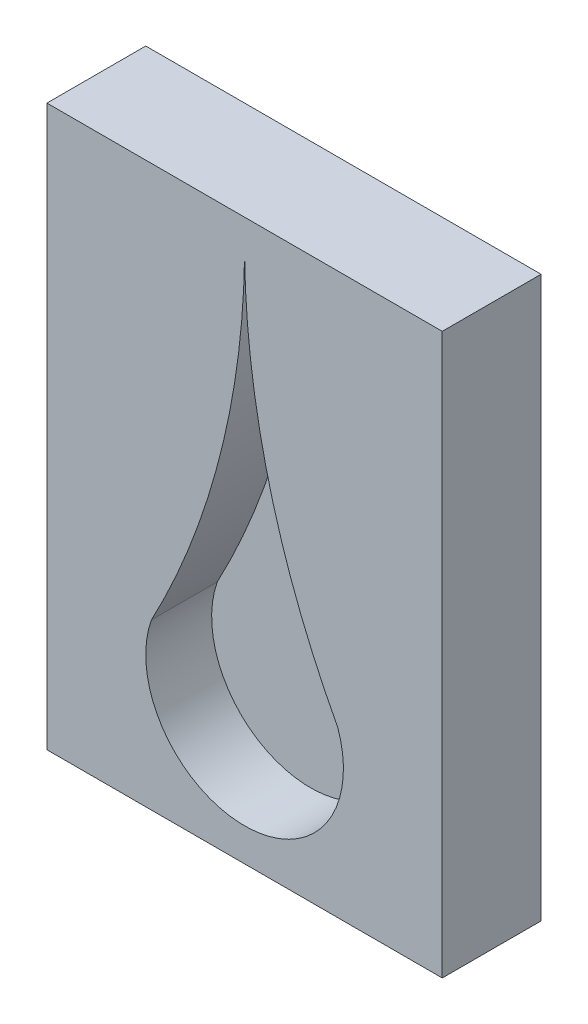
SolidWorks part; units mm, degrees
ref_plane "Front Plane" through (0, 0, 0) normal (0, 0, 1) x (1, 0, 0)
ref_plane "Top Plane" through (0, 0, 0) normal (0, 1, 0) x (1, 0, 0)
ref_plane "Right Plane" through (0, 0, 0) normal (1, 0, 0) x (0, 0, -1)
sketch "Sketch1" plane through (0, 0, 0) normal (0, 0, 1) x (1, 0, 0)
  line L1 (-38.1, -53.975) -> (38.1, -53.975)
  line L2 (-38.1, -53.975) -> (-38.1, 53.975)
  line L3 (-38.1, 53.975) -> (38.1, 53.975)
  line L4 (38.1, -53.975) -> (38.1, 53.975)
  line L5 (-38.1, -53.975) -> (38.1, 53.975) construction
  line L6 (-38.1, 53.975) -> (38.1, -53.975) construction
  point P0 (0, 0)
  dimension "D1" = 76.2
  dimension "D2" = 107.95
extrude "Boss-Extrude1" add sketch "Sketch1" along normal blind 19.05
sketch "Sketch2" plane through (0, 0, 19.05) normal (0, 0, 1) x (1, 0, 0)
  line L1 (0, 0) -> (0, 50000) construction
  line L3 (38.1, 53.975) -> (-38.1, 53.975) construction
  line L4 (-38.1, -53.975) -> (38.1, -53.975) construction
  line L5 (-38.1, 53.975) -> (-38.1, -53.975) construction
  line L6 (-17.9605, -22.225) -> (17.9605, -22.225) construction
  arc A0 (-17.9605, -22.225) -> (17.9605, -22.225) centre (0, -28.575) ccw
  arc A1 (-17.9605, -22.225) -> (0, 47.625) centre (-152.3875, 49.5743) ccw
  arc A2 (17.9605, -22.225) -> (0, 47.625) centre (152.3875, 49.5743) cw
  point P4 (0, 47.625)
  point P12 (-19.05, -28.575)
  point P16 (0, -47.625)
  point P18 (-104.7103, 70.8969)
  dimension "D1" = 6.35
  dimension "D5" = 152.4
  dimension "D2" = 6.35
  dimension "D3" = 19.05
  dimension "D4" = 12.7
extrude "Cut-Extrude1" cut sketch "Sketch2" against normal blind 12.7
sketch "Sketch3" plane through (0, 0, 19.05) normal (0, 0, 1) x (1, 0, 0)
  line L0 (0, 0) -> (0, 50000) construction
  line L1 (0, 0) -> (50000, 0) construction
pattern_linear "LPattern1" [suppressed] count 3 spacing 76.2 along (1, 0, 0) count 2 spacing 107.95 along (0, 1, 0) of bodies 102
